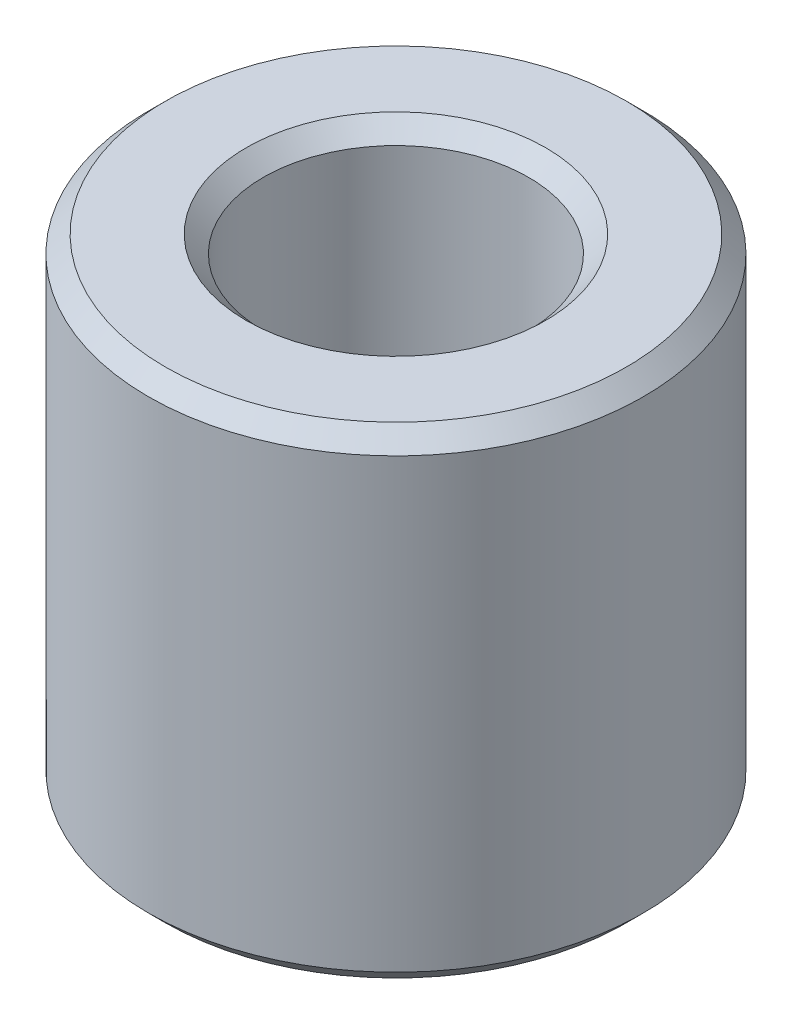
SolidWorks part; units mm, degrees
ref_plane "Front Plane" through (0, 0, 0) normal (0, 0, 1) x (1, 0, 0)
ref_plane "Top Plane" through (0, 0, 0) normal (0, 1, 0) x (1, 0, 0)
ref_plane "Right Plane" through (0, 0, 0) normal (1, 0, 0) x (0, 0, -1)
sketch "Sketch1" plane through (0, 0, 0) normal (0, 1, 0) x (1, 0, 0)
  circle A0 centre (0, 0) radius 50
  dimension "SLEEVE_OD" = 100
extrude "Boss-Extrude1" add sketch "Sketch1" along normal blind 97.2383
sketch "Sketch2" plane through (0, 0, 0) normal (0, 1, 0) x (1, 0, 0)
  circle A0 centre (0, 0) radius 26.7943
  dimension "BORE_D" = 53.5886
extrude "Cut-Extrude1" cut sketch "Sketch2" along normal through all
chamfer "Chamfer1" distance 3.4533 angle 45 4 edges at (0, 97.2383, 26.7943) (0, 0, 26.7943) (0, 0, 50) (0, 97.2383, 50)
